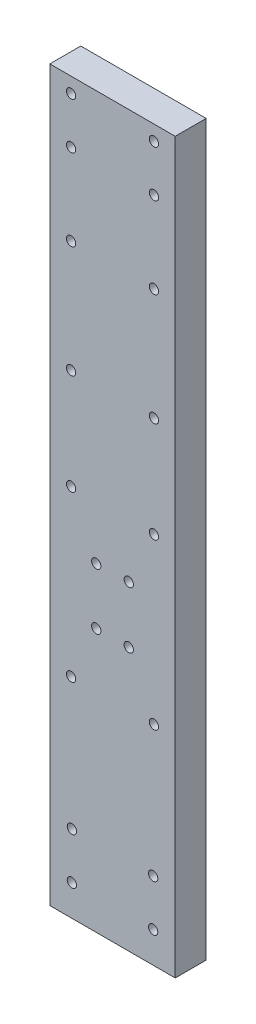
SolidWorks part; units mm, degrees
ref_plane "Front Plane" through (0, 0, 0) normal (0, 0, 1) x (1, 0, 0)
ref_plane "Top Plane" through (0, 0, 0) normal (0, 1, 0) x (1, 0, 0)
ref_plane "Right Plane" through (0, 0, 0) normal (1, 0, 0) x (0, 0, -1)
sketch "Sketch3" plane through (0, 0, 0) normal (0, 0, 1) x (1, 0, 0)
  line L0 (0, 94.0064) -> (0, -0.1536)
  line L1 (16.2, 94.0064) -> (16.2, -0.1536)
  line L2 (0, -0.1536) -> (16.2, -0.1536)
  line L4 (0, 94.0064) -> (16.2, 94.0064)
  line L5 (0, 12.3464) -> (16.2, 12.3464) construction
  line L6 (0, 58.6064) -> (16.2, 58.6064) construction
  line L26 (0, 50.6064) -> (16.2, 50.6064) construction
  line L27 (0, 24.3464) -> (16.2, 24.3464) construction
  line L30 (0, 78.0614) -> (16.2, 78.0614) construction
  line L32 (0, 84.0614) -> (16.2, 84.0614) construction
  circle A0 centre (6, 33.8464) radius 0.6
  circle A1 centre (10.2, 33.8464) radius 0.6
  circle A2 centre (2.75, 86.0614) radius 0.6
  circle A3 centre (10.2, 41.1664) radius 0.6
  circle A4 centre (13.45, 48.1064) radius 0.6
  circle A5 centre (2.75, 92.0614) radius 0.6
  circle A6 centre (13.45, 86.0614) radius 0.6
  circle A7 centre (2.75, 61.1064) radius 0.6
  circle A16 centre (2.85, 9.8464) radius 0.6
  circle A17 centre (13.35, 9.8464) radius 0.6
  circle A18 centre (13.35, 3.8464) radius 0.6
  circle A19 centre (2.85, 3.8464) radius 0.6
  circle A20 centre (13.45, 61.1064) radius 0.6
  circle A21 centre (2.75, 75.5614) radius 0.6
  circle A22 centre (13.45, 26.8464) radius 0.6
  circle A23 centre (13.45, 75.5614) radius 0.6
  circle A24 centre (13.45, 92.0614) radius 0.6
  circle A25 centre (2.75, 26.8464) radius 0.6
  circle A26 centre (6, 41.1064) radius 0.6
  circle A27 centre (2.75, 48.1064) radius 0.6
  dimension "D45" = 1.2
  dimension "D1" = 2.5
  dimension "D2" = 9.5
  dimension "D3" = 2.5
  dimension "D4" = 9.5
  dimension "D5" = 6
  dimension "D6" = 2.75
  dimension "D7" = 2.75
  dimension "D8" = 6
  dimension "D9" = 2.5
  dimension "D10" = 2.5
  dimension "D11" = 9.5
  dimension "D12" = 9.44
  dimension "D13" = 2.75
  dimension "D14" = 6
  dimension "D15" = 2.75
  dimension "D16" = 6
  dimension "D17" = 12
  dimension "D19" = 4
  dimension "D21" = 6
  dimension "D22" = 4
  dimension "D23" = 2.85
  dimension "D24" = 2.85
  dimension "D25" = 26.26
  dimension "D26" = 16.2
  dimension "D27" = 8
  dimension "D28" = 2.5
  dimension "D29" = 2.5
  dimension "D30" = 2.75
  dimension "D31" = 2.75
  dimension "D34" = 2.5
  dimension "D35" = 2.5
  dimension "D36" = 2.75
  dimension "D37" = 2.75
  dimension "D38" = 19.455
  dimension "D39" = 6
  dimension "D40" = 2
  dimension "D41" = 2
  dimension "D42" = 2.75
  dimension "D43" = 2.75
  dimension "D46" = 2.75
  dimension "D47" = 2.75
  dimension "D48" = 9.945
  dimension "D32" = 6
  dimension "D33" = 6
  dimension "D18" = 2.5
  dimension "D44" = 2.5
  dimension "D20" = 6
extrude "Boss-Extrude3" add sketch "Sketch3" along normal blind 4
equation "\"D25@Sketch3\"= \"HL@parametersSketch@prostheticParameters.SLDPRT\" * 0.196 - 4 - 6'Index PIP length"
equation "\"D26@Sketch3\"= \"fingerWidth@parametersSketch@prostheticParameters.SLDPRT\"'Index Width"
equation "\"D38@Sketch3\"= \"HL@parametersSketch@prostheticParameters.SLDPRT\" * 0.143 - 3 - 4 'Index MIP Length"
equation "\"D48@Sketch3\"= \"HL@parametersSketch@prostheticParameters.SLDPRT\" * 0.097 - 3 - 5'Index DIP Length - Gap Fingertip"
equation "\"D45@Sketch3\"= 1 + \"tol1@parametersSketch@prostheticParameters.SLDPRT\""
